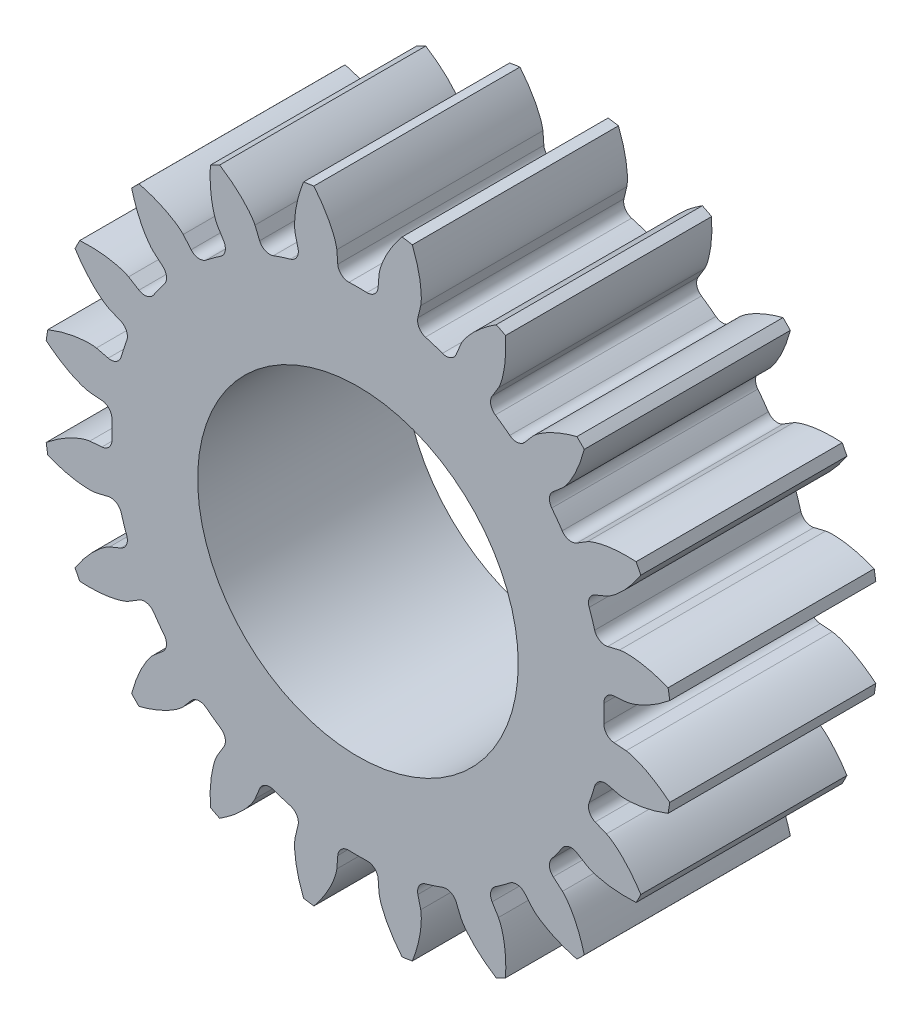
SolidWorks part; units mm, degrees
ref_plane "Front Plane" through (0, 0, 0) normal (0, 0, 1) x (1, 0, 0)
ref_plane "Top Plane" through (0, 0, 0) normal (0, 1, 0) x (1, 0, 0)
ref_plane "Right Plane" through (0, 0, 0) normal (1, 0, 0) x (0, 0, -1)
ref_axis "Gear Axis" through (0, 0, -0.2501) along (0, 0, 1)
sketch "Blank Sketch" plane through (0, 0, 0) normal (0, 0, 1) x (1, 0, 0)
  circle A0 centre (0, 0) radius 13.75
  dimension "OD" = 27.5
extrude "Blank" add sketch "Blank Sketch" along normal blind 9
sketch "Tooth Space Sketch" plane through (0, 0, 0) normal (0, 0, 1) x (1, 0, 0)
  line L0 (11.7099, 0.9227) -> (11.1803, 0.881)
  line L1 (11.7099, -0.9227) -> (11.1803, -0.881)
  line L2 (14.6961, 3.0042) -> (14.6961, -3.0042)
  arc A0 (11.1803, 0.881) -> (10.7429, 0.3902) centre (11.2176, 0.4075) ccw
  arc A1 (10.7429, -0.3902) -> (11.1803, -0.881) centre (11.2176, -0.4075) ccw
  arc A2 (10.7429, -0.3902) -> (10.7429, 0.3902) centre (0, 0) ccw
  spline S0 degree 4 poles (11.7099, 0.9227) (11.7153, 0.9232) (11.7306, 0.925) (11.7593, 0.9294) (11.806, 0.9382) (11.8651, 0.9517) (11.9409, 0.9719) (12.0295, 0.999) (12.1261, 1.0323) (12.2301, 1.0723) (12.3329, 1.1155) (12.4344, 1.1617) (12.5347, 1.2105) (12.6549, 1.2727) (12.7975, 1.3519) (12.9615, 1.4507) (13.1443, 1.5703) (13.3269, 1.7) (13.5034, 1.834) (13.678, 1.9766) (13.8441, 2.1196) (14.0125, 2.2754) (14.1658, 2.4228) (14.3326, 2.5956) (14.4659, 2.7374) (14.6362, 2.9324) (14.7351, 3.0499) (14.8489, 3.1902) (14.8984, 3.2539) (14.9289, 3.293) knots 0 0 0 0 0 0.005377 0.015084 0.028532 0.04661 0.064855 0.092111 0.119476 0.146842 0.174209 0.201575 0.228941 0.256307 0.307035 0.361767 0.4165 0.471232 0.525964 0.580697 0.635429 0.690161 0.744894 0.799626 0.854358 0.909091 0.954545 1 1 1 1 1 construction
  spline S1 degree 4 poles (11.7099, 0.9227) (11.7153, 0.9232) (11.7306, 0.925) (11.7593, 0.9294) (11.806, 0.9382) (11.8651, 0.9517) (11.9409, 0.9719) (12.0295, 0.999) (12.1261, 1.0323) (12.2301, 1.0723) (12.3329, 1.1155) (12.4344, 1.1617) (12.5347, 1.2105) (12.6549, 1.2727) (12.7975, 1.3519) (12.9615, 1.4507) (13.1443, 1.5703) (13.3269, 1.7) (13.5034, 1.834) (13.678, 1.9766) (13.8441, 2.1196) (14.0125, 2.2754) (14.1658, 2.4228) (14.3326, 2.5956) (14.4659, 2.7374) (14.5992, 2.8901) (14.6635, 2.9654) (14.6961, 3.0042) knots 0 0 0 0 0 0.005377 0.015084 0.028532 0.04661 0.064855 0.092111 0.119476 0.146842 0.174209 0.201575 0.228941 0.256307 0.307035 0.361767 0.4165 0.471232 0.525964 0.580697 0.635429 0.690161 0.744894 0.799626 0.854358 0.909091 0.909091 0.909091 0.909091 0.909091
  spline S2 degree 4 poles (11.7099, -0.9227) (11.7153, -0.9232) (11.7306, -0.925) (11.7593, -0.9294) (11.806, -0.9382) (11.8651, -0.9517) (11.9409, -0.9719) (12.0295, -0.999) (12.1261, -1.0323) (12.2301, -1.0723) (12.3329, -1.1155) (12.4344, -1.1617) (12.5347, -1.2105) (12.6549, -1.2727) (12.7975, -1.3519) (12.9615, -1.4507) (13.1443, -1.5703) (13.3269, -1.7) (13.5034, -1.834) (13.678, -1.9766) (13.8441, -2.1196) (14.0125, -2.2754) (14.1658, -2.4228) (14.3326, -2.5956) (14.4659, -2.7374) (14.6362, -2.9324) (14.7351, -3.0499) (14.8489, -3.1902) (14.8984, -3.2539) (14.9289, -3.293) knots 0 0 0 0 0 0.005377 0.015084 0.028532 0.04661 0.064855 0.092111 0.119476 0.146842 0.174209 0.201575 0.228941 0.256307 0.307035 0.361767 0.4165 0.471232 0.525964 0.580697 0.635429 0.690161 0.744894 0.799626 0.854358 0.909091 0.954545 1 1 1 1 1 construction
  spline S3 degree 4 poles (11.7099, -0.9227) (11.7153, -0.9232) (11.7306, -0.925) (11.7593, -0.9294) (11.806, -0.9382) (11.8651, -0.9517) (11.9409, -0.9719) (12.0295, -0.999) (12.1261, -1.0323) (12.2301, -1.0723) (12.3329, -1.1155) (12.4344, -1.1617) (12.5347, -1.2105) (12.6549, -1.2727) (12.7975, -1.3519) (12.9615, -1.4507) (13.1443, -1.5703) (13.3269, -1.7) (13.5034, -1.834) (13.678, -1.9766) (13.8441, -2.1196) (14.0125, -2.2754) (14.1658, -2.4228) (14.3326, -2.5956) (14.4659, -2.7374) (14.5992, -2.8901) (14.6635, -2.9654) (14.6961, -3.0042) knots 0 0 0 0 0 0.005377 0.015084 0.028532 0.04661 0.064855 0.092111 0.119476 0.146842 0.174209 0.201575 0.228941 0.256307 0.307035 0.361767 0.4165 0.471232 0.525964 0.580697 0.635429 0.690161 0.744894 0.799626 0.854358 0.909091 0.909091 0.909091 0.909091 0.909091
  dimension "Root" = 10.75
  dimension "Fillet" = 0.475
extrude "Tooth Space" cut sketch "Tooth Space Sketch" against normal through all both and the other way through all both
pattern_circular "Teeth" count 20 over 360 about axis through (0, 0, -0.2501) along (0, 0, 1) of "Tooth Space"
sketch "Bore Sketch" plane through (0, 0, 0) normal (0, 0, 1) x (1, 0, 0)
  circle A0 centre (0, 0) radius 7
  dimension "Bore" = 14
extrude "Bore" cut sketch "Bore Sketch" against normal through all both and the other way through all both
equation "\"No. of Teeth\"= 20"
equation "\"Module\"= 1.25"
equation "\"Bore Diameter\"= 14"
equation "\"Pressure Angle\"= 20"
equation "\"Outer Diameter\"= ( \"No. of Teeth\" + 2 ) * \"Module\""
equation "\"Pitch Diameter\"= \"No. of Teeth\" * \"Module\""
equation "\"Backlash\"= 0.3 * \"Module\""
equation "\"Arc Length\"= ( ( \"Module\" * pi ) / 2 + \"Backlash\" )"
equation "\"Fillet Radius\"= 0.38 * \"Module\""
equation "\"Tooth Depth\"= IIF ( \"Module\" <= 1.25 , \"Module\" * 2.4 , \"Module\" * 2.25 )"
equation "\"Face Width\"= 9"
equation "\"Root Diameter\"= \"Outer Diameter\" - 2 * \"Tooth Depth\""
equation "\"Base Diameter\"= \"Pitch Diameter\" * cos ( \"Pressure Angle\" )"
equation "\"Base Radius\"= \"Base Diameter\" / 2"
equation "\"Tooth Thickness\"= \"Module\" * pi - \"Arc Length\""
equation "\"Half Space Angle\"= ( \"Arc Length\" / \"Pitch Diameter\" ) * 180 / pi"
equation "\"Involute Fn\"= tan ( \"Pressure Angle\" ) - \"Pressure Angle\" * pi / 180"
equation "\"Flank Offset\"= \"Arc Length\" / \"Pitch Diameter\" - \"Involute Fn\""
equation "\"Tip Cap Diameter\"= \"Outer Diameter\" + 2 * \"Module\""
equation "\"Flank Start Diameter\"= IIF ( \"Base Diameter\" >= ( \"Root Diameter\" + 3 * \"Fillet Radius\" ) , \"Base Diameter\" , \"Root Diameter\" + 3 * \"Fillet Radius\" )"
equation "\"Involute t1\"= ( abs ( ( \"Flank Start Diameter\" / \"Base Diameter\" ) ^ 2 - 1 ) ) ^ 0.5"
equation "\"Involute t2\"= ( abs ( ( \"Tip Cap Diameter\" / \"Base Diameter\" ) ^ 2 - 1 ) ) ^ 0.5"
equation "\"Flank Arc Radius\"= ( \"Pitch Diameter\" / 2 ) * sin ( \"Pressure Angle\" )"
equation "\"Flank Centre Angle\"= \"Half Space Angle\" + \"Pressure Angle\""
equation "\"OD@Blank Sketch\"= \"Outer Diameter\""
equation "\"Width@Blank\"= \"Face Width\""
equation "\"Root@Tooth Space Sketch\"= \"Root Diameter\" / 2"
equation "\"Fillet@Tooth Space Sketch\"= \"Fillet Radius\""
equation "\"Count@Teeth\"= \"No. of Teeth\""
equation "\"Bore@Bore Sketch\"= \"Bore Diameter\""
